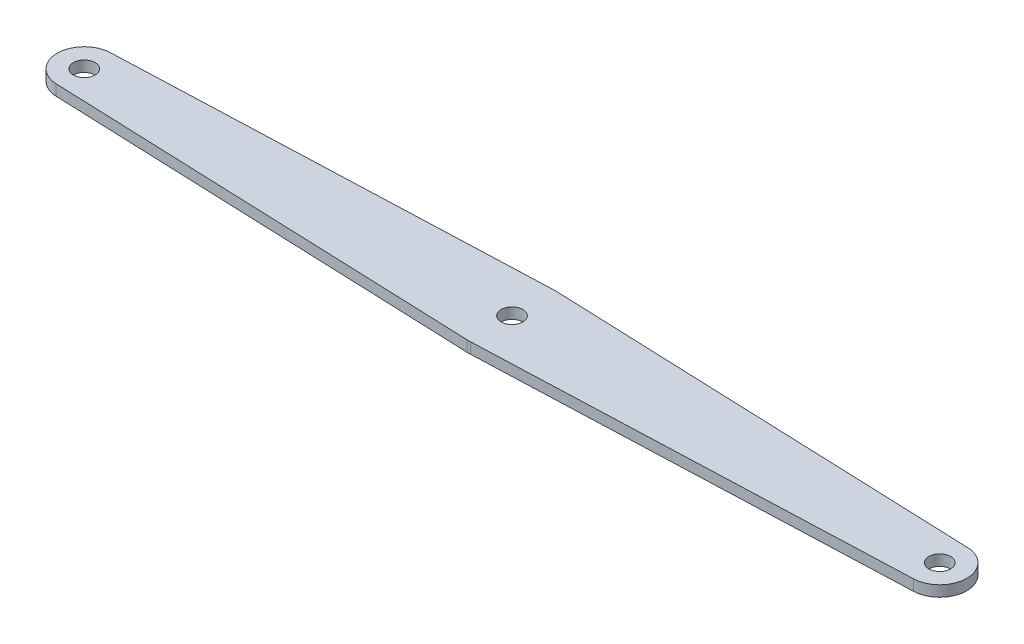
SolidWorks part; units mm, degrees
ref_plane "Спереди" through (0, 0, 0) normal (0, 0, 1) x (1, 0, 0)
ref_plane "Сверху" through (0, 0, 0) normal (0, 1, 0) x (1, 0, 0)
ref_plane "Справа" through (0, 0, 0) normal (1, 0, 0) x (0, 0, -1)
sketch "Эскиз1" plane through (0, 0, 0) normal (0, 1, 0) x (1, 0, 0)
  line L0 (-79, 0) -> (79, 0) construction
  line L1 (-79.1899, 4.9964) -> (-0.3038, 7.9942)
  line L2 (-79.1899, -4.9964) -> (-0.3038, -7.9942)
  line L3 (0.3038, 7.9942) -> (79.1899, 4.9964)
  line L4 (-0.3038, -7.9942) -> (0.3038, -7.9942)
  line L5 (79.1899, -4.9964) -> (0.3038, -7.9942)
  line L6 (-0.3038, 7.9942) -> (0.3038, 7.9942)
  arc A0 (0.3038, 7.9942) -> (-0.3038, 7.9942) centre (0, 0) ccw construction
  arc A1 (-79.1899, 4.9964) -> (-79.1899, -4.9964) centre (-79, 0) ccw
  arc A2 (79.1899, -4.9964) -> (79.1899, 4.9964) centre (79, 0) ccw
  arc A3 (-0.3038, -7.9942) -> (0.3038, -7.9942) centre (0, 0) ccw construction
  point P7 (0, 0)
  dimension "D2" = 8
  dimension "D3" = 5
  dimension "D1" = 158
extrude "тело" add sketch "Эскиз1" along normal blind 2
sketch "Эскиз2" plane through (0, 2, 0) normal (0, 1, 0) x (1, 0, 0)
  circle A0 centre (0, 0) radius 2
  dimension "D1" = 4
extrude "отверстие под ось вращения" cut sketch "Эскиз2" against normal through all
sketch "Эскиз3" plane through (0, 2, 0) normal (0, 1, 0) x (1, 0, 0)
  circle A0 centre (-79, 0) radius 2
  circle A1 centre (79, 0) radius 2
  dimension "D1" = 4
extrude "отверстие для крепления тягов" cut sketch "Эскиз3" against normal through all
